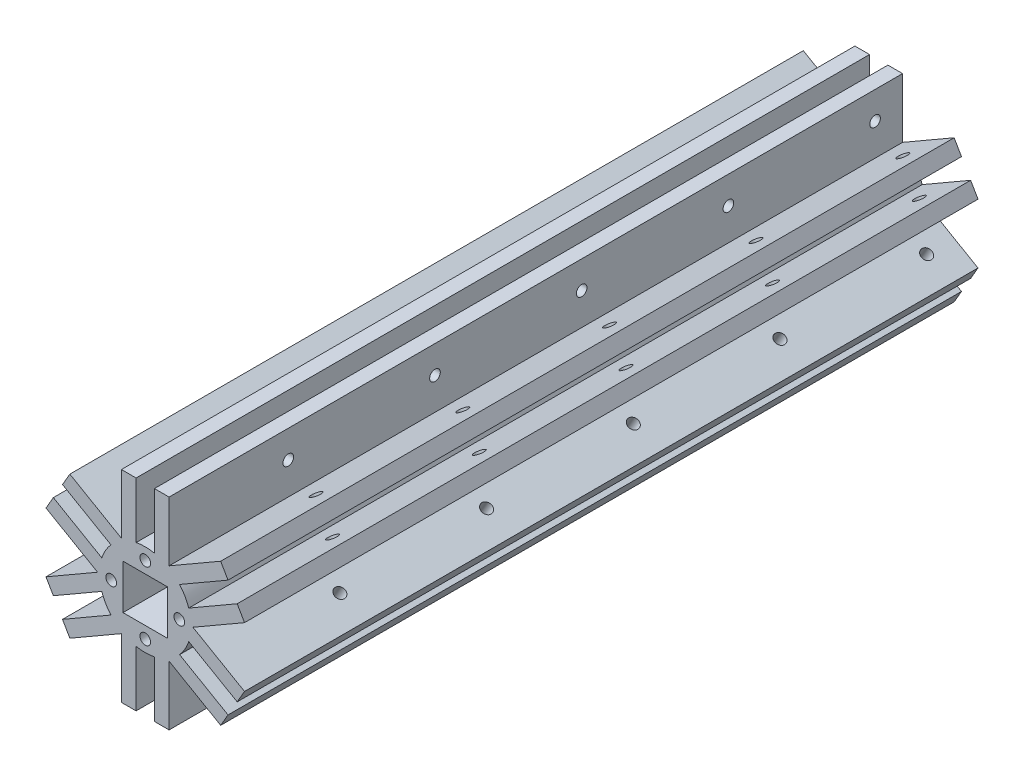
SolidWorks part; units mm, degrees
ref_plane "Front Plane" through (0, 0, 0) normal (0, 0, 1) x (1, 0, 0)
ref_plane "Top Plane" through (0, 0, 0) normal (0, 1, 0) x (1, 0, 0)
ref_plane "Right Plane" through (0, 0, 0) normal (1, 0, 0) x (0, 0, -1)
sketch "Sketch1" plane through (0, 0, 0) normal (0, 0, 1) x (1, 0, 0)
  circle A0 centre (0, 0) radius 12.5
  dimension "D2" = 25
extrude "Boss-Extrude1" add sketch "Sketch1" along normal mid plane 200
sketch "Sketch4" plane through (0, 0, 100) normal (0, 0, 1) x (1, 0, 0)
  line L0 (8.25, 0) -> (-8.25, 0) construction
  line L2 (-6.5, 0) -> (-2.5, 0)
  line L3 (0, 0) -> (0, 15.8331) construction
  line L4 (-6.5, 0) -> (-6.5, 27.5)
  line L5 (-6.5, 27.5) -> (-2.5, 27.5)
  line L6 (-2.5, 0) -> (-2.5, 27.5)
  line L7 (0, -8.25) -> (0, 8.25) construction
  line L8 (6.5, 27.5) -> (2.5, 27.5)
  line L9 (2.5, 0) -> (2.5, 27.5)
  line L10 (6.5, 0) -> (2.5, 0)
  line L11 (6.5, 0) -> (6.5, 27.5)
  dimension "D1" = 27.5
  dimension "D3" = 2.5
  dimension "D2" = 4
extrude "Boss-Extrude3" add sketch "Sketch4" against normal up to surface (200 mm away) up to face at (12.5, 0, -100)
pattern_circular "CirPattern7" count 6 over 360 about axis through (0, 0, -100) along (0, 0, 1) of "Boss-Extrude3"
sketch "Sketch7" plane through (-6.5, 0, 0) normal (-1, 0, 0) x (0, 0, 1)
  line L0 (-100, 27.5) -> (100, 27.5) construction
  line L1 (-100, 11.2583) -> (-100, 27.5) construction
  circle A0 centre (-92.5, 20) radius 1.45
  circle A1 centre (-52.5, 20) radius 1.45
  circle A2 centre (-12.5, 20) radius 1.45
  circle A3 centre (27.5, 20) radius 1.45
  circle A4 centre (67.5, 20) radius 1.45
  dimension "D1" = 2.9
  dimension "D2" = 7.5
  dimension "D3" = 7.5
  dimension "D4" = 5
extrude "Cut-Extrude2" cut sketch "Sketch7" against normal blind 17
pattern_circular "CirPattern9" count 6 over 360 about axis through (0, 0, 100) along (0, 0, 1) of "Cut-Extrude2"
sketch "Sketch8" plane through (0, 0, 100) normal (0, 0, 1) x (1, 0, 0)
  line L2 (-6.075, 6.075) -> (6.075, 6.075)
  line L3 (-6.075, 6.075) -> (-6.075, -6.075)
  line L4 (-6.075, -6.075) -> (6.075, -6.075)
  line L5 (6.075, 6.075) -> (6.075, -6.075)
  line L6 (-6.075, 6.075) -> (6.075, -6.075) construction
  line L7 (-6.075, -6.075) -> (6.075, 6.075) construction
  point P5 (0, 0)
  point P14 (0, 0)
  dimension "D1" = 12.15
extrude "Cut-Extrude3" cut sketch "Sketch8" against normal up to next
sketch "Sketch9" plane through (0, 0, 100) normal (0, 0, 1) x (1, 0, 0)
  line L0 (8.25, 0) -> (-8.25, 0) construction
  line L1 (6.075, -6.075) -> (6.075, 6.075) construction
  circle A0 centre (9.2875, 0) radius 1.45
  circle A1 centre (0, -9.2875) radius 1.45
  circle A2 centre (-9.2875, 0) radius 1.45
  circle A3 centre (0, 9.2875) radius 1.45
  point P14 (0, 0)
  dimension "D1" = 2.9
  dimension "D2" = 3.2125
  dimension "D3" = 4
extrude "Cut-Extrude4" cut sketch "Sketch9" against normal blind 10
equation "\"drumDiameter\" = 25"
equation "\"D2@Sketch1\"=\"drumDiameter\""
equation "\"drumLength\" = 200"
equation "\"D1@Sketch4\"=\"drumDiameter\"*(0.5+\"drumAbove\")"
equation "\"foamThickness\" = 5"
equation "\"D3@Sketch4\"=\"foamThickness\"/2"
equation "\"drumAbove\"= 0.6"
equation "\"D2@Sketch7\"=\"drumDiameter\"*\"drumAbove\"/2"
equation "\"holderThicc\" = 4"
equation "\"D2@Sketch4\"=\"holderThicc\""
equation "\"D1@Boss-Extrude1\"=\"drumLength\""
equation "\"squareBarLength\"=12.15"
equation "\"D1@Sketch8\"=\"squareBarLength\""
equation "\"D2@Sketch9\"=(\"drumDiameter\"/2-\"squareBarLength\"/2)/2"
